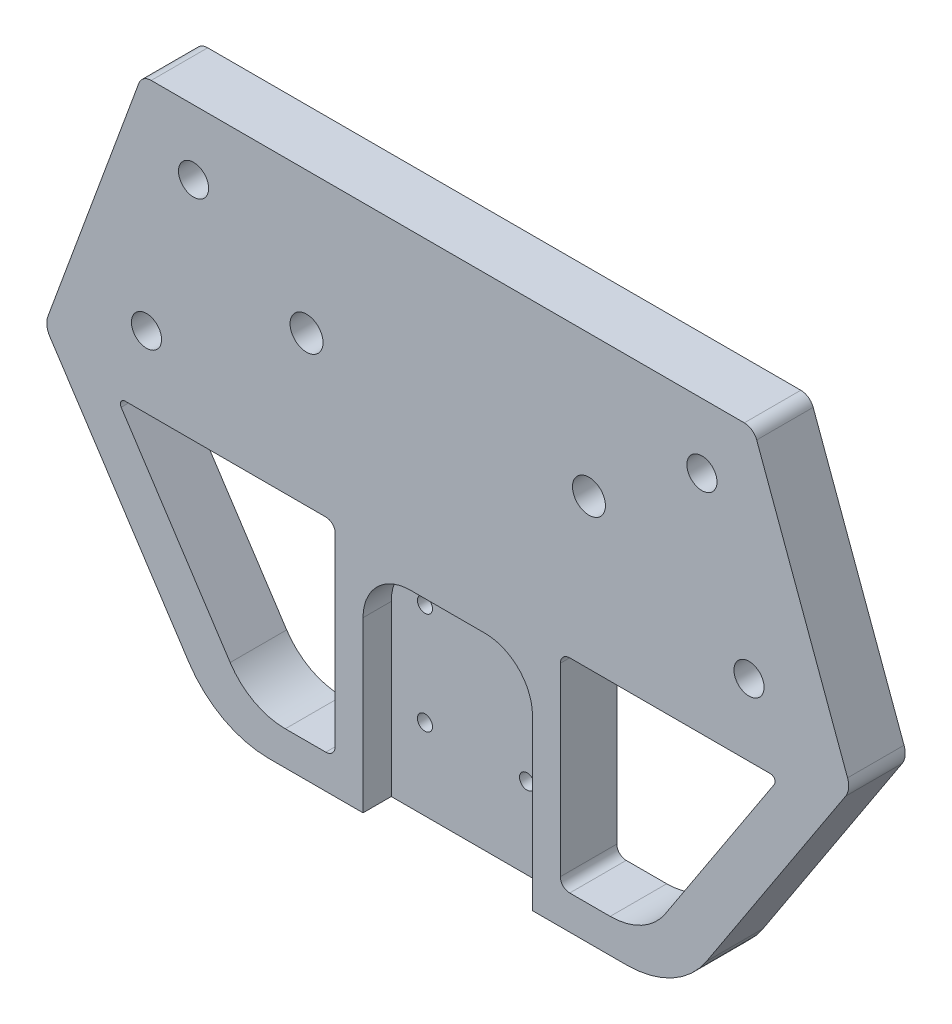
SolidWorks part; units mm, degrees
ref_plane "Front Plane" through (0, 0, 0) normal (0, 0, 1) x (1, 0, 0)
ref_plane "Top Plane" through (0, 0, 0) normal (0, 1, 0) x (1, 0, 0)
ref_plane "Right Plane" through (0, 0, 0) normal (1, 0, 0) x (0, 0, -1)
sketch "Sketch2" plane through (0, 0, 0) normal (0, 0, 1) x (1, 0, 0)
  line L0 (0, -44.7145) -> (0, 43.9236) construction
  line L3 (-53.9331, -0.3154) -> (-41.6738, 33.03)
  line L5 (-53.6746, -2.5826) -> (-34.912, -31.257)
  line L8 (-24.13, -37.0871) -> (24.13, -37.0871)
  line L9 (-40.005, 34.1945) -> (40.005, 34.1945)
  line L10 (53.6746, -2.5826) -> (34.912, -31.257)
  line L11 (53.9331, -0.3154) -> (41.6738, 33.03)
  arc A1 (-40.005, 34.1945) -> (-41.6738, 33.03) centre (-40.005, 32.4165) ccw
  circle A4 centre (-19.05, 15.1445) radius 2.2225
  arc A6 (-24.13, -37.0871) -> (-34.912, -31.257) centre (-24.13, -24.202) cw
  arc A8 (-53.6746, -2.5826) -> (-53.9331, -0.3154) centre (-51.5491, -1.1919) cw
  arc A10 (53.6746, -2.5826) -> (53.9331, -0.3154) centre (51.5491, -1.1919) ccw
  arc A11 (24.13, -37.0871) -> (34.912, -31.257) centre (24.13, -24.202) ccw
  circle A12 centre (19.05, 15.1445) radius 2.2225
  arc A13 (40.005, 34.1945) -> (41.6738, 33.03) centre (40.005, 32.4165) cw
  point P4 (0, 57.6776)
  point P9 (0, 19.5776)
  point P12 (54.3738, -1.514)
  point P13 (0, -37.0871)
  point P19 (-31.0972, -37.0871)
  point P20 (0, -3.9055)
  point P28 (-54.3738, -1.514)
  point P33 (0, 34.1945)
  point P34 (31.0972, -37.0871)
  dimension "D2" = 1.778
  dimension "D3" = 12.8851
  dimension "D6" = 24.13
  dimension "D4" = 2.54
  dimension "D5" = 19.05
  dimension "D7" = 31.0972
  dimension "D8" = 40.005
  dimension "D9" = 41.6738
  dimension "D10" = 51.5491
  dimension "D11" = 15.1445
  dimension "D12" = 19.5776
  dimension "D1" = 4.445
  dimension "D13" = 32.4165
  dimension "D14" = 57.6776
extrude "Boss-Extrude1" add sketch "Sketch2" along normal blind 7.62
sketch "Sketch3" plane through (0, 0, 7.62) normal (0, 0, 1) x (1, 0, 0)
  line L0 (0, 22.8554) -> (0, -43.592) construction
  line L7 (-24.13, -37.0871) -> (24.13, -37.0871) construction
  circle A0 centre (-6.887, -26.1651) radius 1.016
  circle A1 centre (-6.887, -12.3912) radius 1.016
  circle A6 centre (6.887, -12.3912) radius 1.016
  circle A7 centre (6.887, -26.1651) radius 1.016
  dimension "D4" = 10.922
  dimension "D1" = 6.887
  dimension "D2" = 13.7739
  dimension "D3" = 2.032
extrude "Cut-Extrude1" cut sketch "Sketch3" against normal through all both and the other way through all
sketch "Sketch4" plane through (0, 0, 7.62) normal (0, 0, 1) x (1, 0, 0)
  line L0 (0, 3.0374) -> (0, -49.2989) construction
  line L1 (5.0189, -7.8763) -> (-5.0189, -7.8763)
  line L2 (-11.43, -14.2874) -> (-11.43, -37.7213)
  line L3 (-11.43, -37.7213) -> (11.43, -37.7213)
  line L4 (-24.13, -37.0871) -> (24.13, -37.0871) construction
  line L5 (11.43, -14.2874) -> (11.43, -37.7213)
  arc A0 (-5.0189, -7.8763) -> (-11.43, -14.2874) centre (-5.0189, -14.2874) ccw
  arc A1 (5.0189, -7.8763) -> (11.43, -14.2874) centre (5.0189, -14.2874) cw
  point P9 (-11.43, -7.8763)
  point P14 (0, -7.8763)
  point P17 (0, -37.7213)
  dimension "D1" = 11.43
  dimension "D3" = 29.845
  dimension "D4" = 0.6343
extrude "Cut-Extrude2" cut sketch "Sketch4" against normal blind 3.81 and the other way through all
sketch "Sketch5" plane through (0, 0, 0) normal (0, 0, -1) x (-1, 0, 0)
  line L0 (0, -24.2327) -> (0, 20.0285) construction
  circle A0 centre (-6.887, -12.3912) radius 1.905
  circle A1 centre (-6.887, -26.1651) radius 1.905
  circle A2 centre (6.887, -26.1651) radius 1.905
  circle A3 centre (6.887, -12.3912) radius 1.905
  dimension "D1" = 3.81
  dimension "D2" = 3.81
extrude "Cut-Extrude3" cut sketch "Sketch5" against normal blind 1.3335
sketch "Sketch6" plane through (0, 0, 7.62) normal (0, 0, 1) x (1, 0, 0)
  line L0 (0, -25.1696) -> (0, 28.2164) construction
  line L3 (-44.0566, -6.0154) -> (-29.3539, -28.4854)
  line L4 (-53.6746, -2.5826) -> (-34.912, -31.257) construction
  line L5 (-54.0728, -1.4797) -> (0, -1.4797) construction
  line L6 (-43.5253, -5.0327) -> (-16.453, -5.0327)
  line L7 (-15.183, -6.3027) -> (-15.183, -31.2378)
  line L8 (-16.453, -32.5078) -> (-21.9149, -32.5078)
  line L9 (16.453, -32.5078) -> (21.9149, -32.5078)
  line L10 (15.183, -6.3027) -> (15.183, -31.2378)
  line L11 (43.5253, -5.0327) -> (16.453, -5.0327)
  line L12 (44.0566, -6.0154) -> (29.3539, -28.4854)
  line L15 (-11.43, -14.2874) -> (-11.43, -37.0871) construction
  line L16 (11.43, -37.0871) -> (24.13, -37.0871) construction
  arc A3 (-53.9331, -0.3154) -> (-53.6746, -2.5826) centre (-51.5491, -1.1919) ccw construction
  arc A4 (-21.9149, -32.5078) -> (-29.3539, -28.4854) centre (-21.9149, -23.6178) cw
  arc A5 (-15.183, -31.2378) -> (-16.453, -32.5078) centre (-16.453, -31.2378) cw
  arc A6 (-15.183, -6.3027) -> (-16.453, -5.0327) centre (-16.453, -6.3027) ccw
  arc A7 (-43.5253, -5.0327) -> (-44.0566, -6.0154) centre (-43.5253, -5.6677) ccw
  arc A8 (43.5253, -5.0327) -> (44.0566, -6.0154) centre (43.5253, -5.6677) cw
  arc A9 (15.183, -6.3027) -> (16.453, -5.0327) centre (16.453, -6.3027) cw
  arc A10 (15.183, -31.2378) -> (16.453, -32.5078) centre (16.453, -31.2378) ccw
  arc A11 (21.9149, -32.5078) -> (29.3539, -28.4854) centre (21.9149, -23.6178) ccw
  dimension "D1" = 8.89
  dimension "D2" = 35.56
  dimension "D3" = 3.753
  dimension "D4" = 0.635
  dimension "D8" = 1.27
  dimension "D5" = 10.4849
  dimension "D6" = 32.0953
  dimension "D7" = 4.5793
  dimension "D9" = 22.7997
extrude "Cut-Extrude4" cut sketch "Sketch6" against normal through all
sketch "Sketch8" plane through (0, 0, 7.62) normal (0, 0, 1) x (1, 0, 0)
  line L0 (0, 24.5882) -> (0, -31.804) construction
  line L1 (-16.453, -5.0327) -> (-43.5253, -5.0327) construction
  circle A0 centre (-40.64, 4.6193) radius 2.032
  circle A1 centre (-34.29, 25.4473) radius 2.032
  circle A2 centre (40.64, 4.6193) radius 2.032
  circle A3 centre (34.29, 25.4473) radius 2.032
  dimension "D1" = 4.064
  dimension "D2" = 4.064
  dimension "D3" = 40.64
  dimension "D4" = 34.29
  dimension "D5" = 9.652
  dimension "D6" = 30.48
extrude "Cut-Extrude6" cut sketch "Sketch8" against normal through all
sketch "Sketch9" plane through (0, 0, 0) normal (0, 0, -1) x (-1, 0, 0)
  line L0 (0, -8.3025) -> (0, 31.5976) construction
  circle A0 centre (-19.05, 15.1445) radius 3.937
  circle A1 centre (19.05, 15.1445) radius 3.937
  dimension "D1" = 7.874
extrude "Cut-Extrude7" cut sketch "Sketch9" against normal blind 2.286
